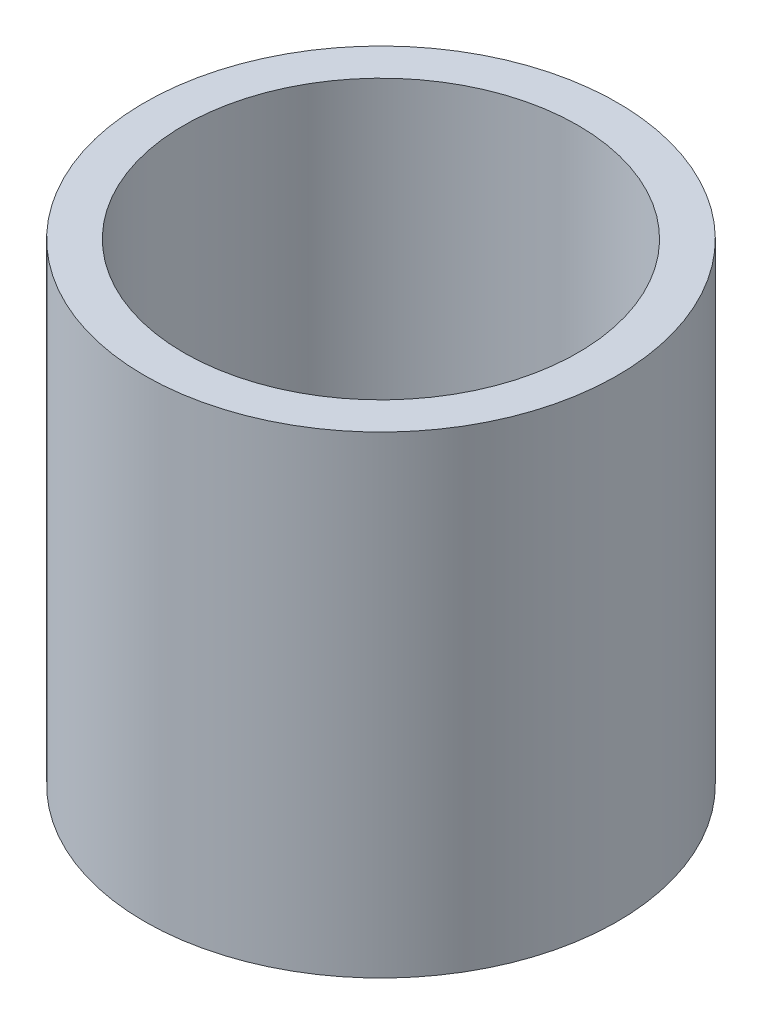
SolidWorks part; units mm, degrees
ref_plane "Front Plane" through (0, 0, 0) normal (0, 0, 1) x (1, 0, 0)
ref_plane "Top Plane" through (0, 0, 0) normal (0, 1, 0) x (1, 0, 0)
ref_plane "Right Plane" through (0, 0, 0) normal (1, 0, 0) x (0, 0, -1)
sketch "Sketch1" plane through (0, 0, 0) normal (0, 1, 0) x (1, 0, 0)
  circle A0 centre (0, 0) radius 3
  circle A1 centre (0, 0) radius 2.5
  dimension "D1" = 6
  dimension "D2" = 5
extrude "Boss-Extrude1" add sketch "Sketch1" along normal blind 6
